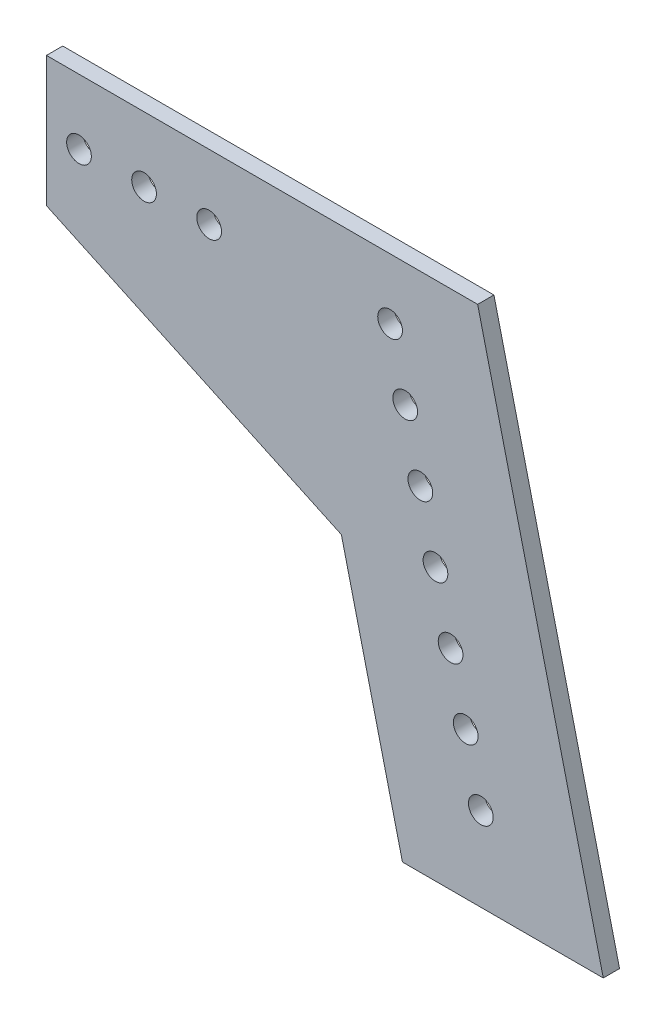
SolidWorks part; units mm, degrees
ref_plane "Front Plane" through (0, 0, 0) normal (0, 0, 1) x (1, 0, 0)
ref_plane "Top Plane" through (0, 0, 0) normal (0, 1, 0) x (1, 0, 0)
ref_plane "Right Plane" through (0, 0, 0) normal (1, 0, 0) x (0, 0, -1)
sketch "Sketch1" plane through (0, 0, 0) normal (0, 0, 1) x (1, 0, 0)
  line L1 (-190.5, -88.9) -> (190.5, -88.9)
  line L2 (-190.5, -88.9) -> (-190.5, 88.9)
  line L3 (-190.5, 88.9) -> (190.5, 88.9)
  line L4 (190.5, -88.9) -> (190.5, 88.9)
  dimension "D1" = 381
  dimension "D2" = 177.8
extrude "Boss-Extrude1" add sketch "Sketch1" along normal blind 3.175
sketch "Sketch3" plane through (0, 0, 0) normal (0, 0, -1) x (-1, 0, 0)
  line L7 (-133.1401, -83.5308) -> (-95.5604, 72.2062) construction
  line L8 (-223.5893, -458.3689) -> (-104.4279, 35.4576) construction
  line L9 (187.2332, -70.9445) -> (149.6535, 84.7925) construction
  line L10 (161.6214, 35.1951) -> (280.6439, -458.0557) construction
  line L11 (-190.5, 88.9) -> (-99.3708, 88.9)
  line L12 (-190.5, 88.9) -> (190.5, 88.9) construction
  line L13 (-99.3708, 88.9) -> (-190.5, -288.7557)
  line L14 (-190.5, -288.7557) -> (-190.5, 88.9)
  line L15 (258.6308, 88.9) -> (156.501, 88.9)
  line L16 (156.501, 88.9) -> (258.6308, -334.3442)
  line L17 (258.6308, -334.3442) -> (258.6308, 88.9)
  dimension "D1" = 7.62
  dimension "D2" = 7.62
extrude "Cut-Extrude1" cut sketch "Sketch3" against normal through all
sketch "Sketch4" plane through (0, 0, 0) normal (0, 0, -1) x (-1, 0, 0)
  line L0 (201.949, -63.5) -> (-149.0579, -63.5)
  line L3 (-149.0579, -63.5) -> (-154.4804, -88.9)
  line L4 (-154.4804, -88.9) -> (207.1627, -88.9)
  line L5 (207.1627, -88.9) -> (201.949, -63.5)
  line L6 (190.5, -88.9) -> (-142.2744, -88.9) construction
  dimension "D1" = 25.4
extrude "Cut-Extrude2" cut sketch "Sketch4" against normal through all
sketch "Sketch8" plane through (0, 0, 0) normal (0, 0, -1) x (-1, 0, 0)
  line L0 (-96.9518, -63.5) -> (-85.0324, -14.1181)
  line L1 (190.5, -63.5) -> (-136.1453, -63.5) construction
  line L2 (-85.0324, -14.1181) -> (194.3676, -14.1181)
  line L3 (194.3676, -14.1181) -> (206.287, -63.5)
  line L4 (206.287, -63.5) -> (-96.9518, -63.5)
  dimension "D2" = 103.57
  dimension "D3" = 279.4
  dimension "D4" = 50.8
  dimension "D5" = 76.43
extrude "Cut-Extrude3" cut sketch "Sketch8" against normal through all
sketch "Sketch9" plane through (0, 0, 0) normal (0, 0, -1) x (-1, 0, 0)
  line L0 (-117.7822, -70.0483) -> (-79.4277, 88.9) construction
  line L1 (-99.3708, 88.9) -> (156.501, 88.9) construction
  line L4 (-136.1453, -63.5) -> (-99.3708, 88.9) construction
  line L5 (-136.1453, -63.5) -> (-99.3708, 88.9) construction
  circle A0 centre (-112.2489, -47.117) radius 2.413
  circle A1 centre (-109.2968, -34.8832) radius 2.413
  circle A2 centre (-106.3448, -22.6495) radius 2.413
  circle A3 centre (-103.3928, -10.4158) radius 2.413
  circle A4 centre (-100.4407, 1.818) radius 2.413
  circle A5 centre (-97.4887, 14.0517) radius 2.413
  circle A6 centre (-94.5367, 26.2855) radius 2.413
  circle A7 centre (-91.5847, 38.5192) radius 2.413 construction
  circle A8 centre (-88.6326, 50.753) radius 2.413 construction
  circle A9 centre (-85.6806, 62.9867) radius 2.413
  circle A10 centre (-82.7286, 75.2205) radius 2.413
  ellipse E0 centre (-117.4825, -72.4407) end of major axis (-116.9164, -70.095) minor radius 2.3977 construction
  dimension "D1" = 4.826
  dimension "D2" = 19.3868
  dimension "D4" = 13.6795
  dimension "D3" = 11
extrude "Cut-Extrude5" cut sketch "Sketch9" against normal through all
sketch "Sketch10" plane through (0, 0, 0) normal (0, 0, -1) x (-1, 0, 0)
  line L0 (-99.3708, 88.9) -> (-111.629, 38.1)
  line L1 (-136.1453, -63.5) -> (-99.3708, 88.9) construction
  line L2 (-111.629, 38.1) -> (168.7592, 38.1)
  line L4 (156.501, 88.9) -> (181.3595, -14.1181) construction
  line L5 (168.7592, 38.1) -> (156.501, 88.9)
  line L6 (156.501, 88.9) -> (-99.3708, 88.9)
  dimension "D1" = 50.8
extrude "Cut-Extrude6" cut sketch "Sketch10" against normal through all
sketch "Sketch11" plane through (0, 0, 0) normal (0, 0, -1) x (-1, 0, 0)
  line L0 (-85.0324, -14.1181) -> (-27.4734, 12.7)
  line L1 (-27.4734, 12.7) -> (-27.4734, 38.1)
  line L2 (-111.629, 38.1) -> (168.7592, 38.1) construction
  line L5 (-27.4734, 38.1) -> (60.9592, 38.1)
  line L6 (132.284, -14.1181) -> (-85.0324, -14.1181)
  line L7 (60.9592, 38.1) -> (169.9103, 38.1)
  line L8 (169.9103, 38.1) -> (200.7912, -67.4952)
  line L9 (200.7912, -67.4952) -> (145.1677, -67.4952)
  line L10 (145.1677, -67.4952) -> (132.284, -14.1181)
  dimension "D1" = 25.4
  dimension "D2" = 63.5
extrude "Cut-Extrude7" cut sketch "Sketch11" against normal through all
sketch "Sketch12" plane through (0, 0, 0) normal (0, 0, -1) x (-1, 0, 0)
  line L0 (-27.4734, 38.1) -> (-27.4734, 12.7) construction
  line L1 (-65.5734, 12.7) -> (124.9266, 12.7) construction
  circle A0 centre (-33.8234, 25.4) radius 2.413
  circle A1 centre (-46.5234, 25.4) radius 2.413
  circle A2 centre (-59.2234, 25.4) radius 2.413
  dimension "D1" = 4.826
  dimension "D2" = 6.35
  dimension "D3" = 12.7
  dimension "D4" = 3
extrude "Cut-Extrude8" cut sketch "Sketch12" against normal through all
sketch "Sketch7" plane through (0, 0, 0) normal (0, 0, -1) x (-1, 0, 0)
  line L0 (-142.1813, -63.5) -> (-127.8939, -16.9599)
  line L1 (179.0525, -63.5) -> (-177.122, -63.5) construction
  line L2 (-127.8939, -16.9599) -> (126.8526, -16.9599)
  line L3 (126.8526, -16.9599) -> (140.6477, -63.5)
  line L4 (140.6477, -63.5) -> (-142.1813, -63.5)
sketch "Sketch6" plane through (0, 0, 0) normal (0, 0, -1) x (-1, 0, 0)
  line L0 (-140.8106, -63.5) -> (-127.3051, -19.1804)
  line L1 (179.0525, -63.5) -> (-177.122, -63.5) construction
  line L2 (-127.3051, -19.1804) -> (124.3177, -19.1804)
  line L3 (124.3177, -19.1804) -> (136.9873, -63.5)
